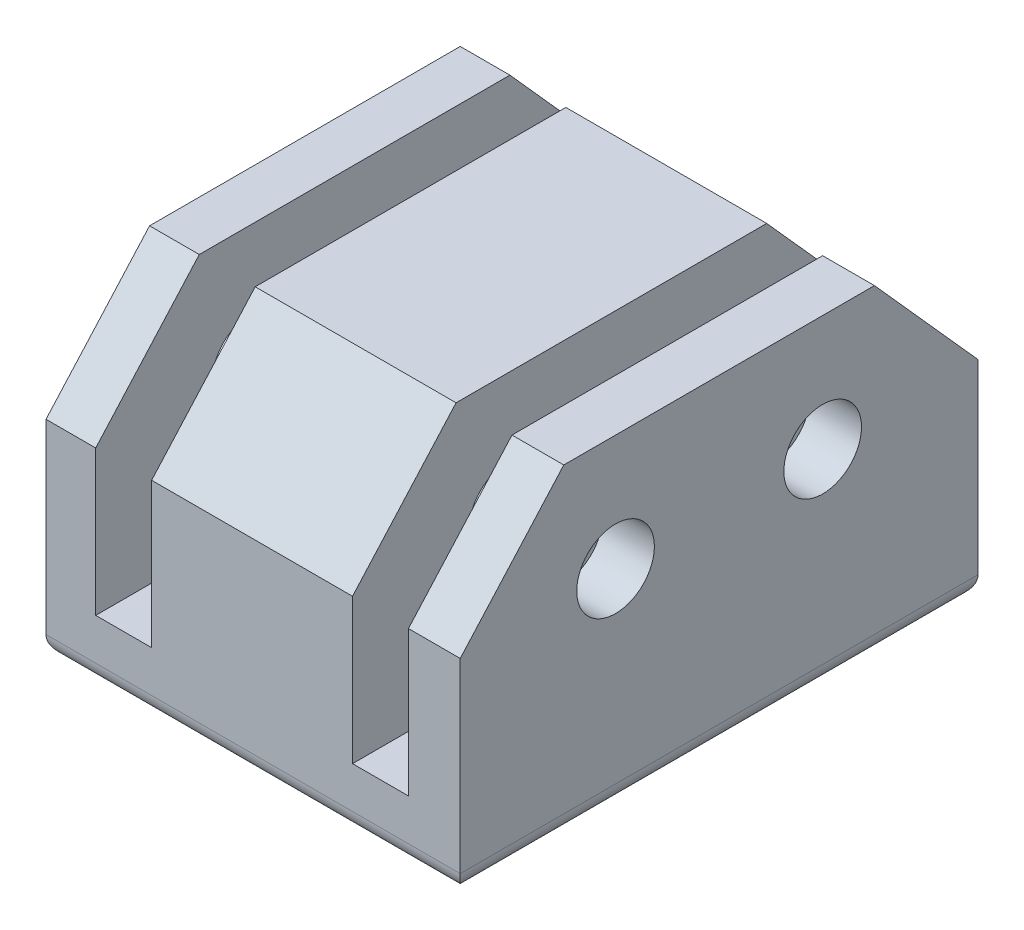
SolidWorks part; units mm, degrees
ref_plane "Front Plane" through (0, 0, 0) normal (0, 0, 1) x (1, 0, 0)
ref_plane "Top Plane" through (0, 0, 0) normal (0, 1, 0) x (1, 0, 0)
ref_plane "Right Plane" through (0, 0, 0) normal (1, 0, 0) x (0, 0, -1)
sketch "Sketch1" plane through (0, 0, 0) normal (1, 0, 0) x (0, 0, -1)
  line L1 (0, 0) -> (63.5, 0)
  line L2 (0, 0) -> (0, 6.35)
  line L3 (0, 6.35) -> (63.5, 6.35)
  line L4 (63.5, 0) -> (63.5, 6.35)
  dimension "D1" = 6.35
  dimension "D2" = 63.5
extrude "Boss-Extrude1" add sketch "Sketch1" against normal blind 50.8
sketch "Sketch2" plane through (0, 0, 0) normal (1, 0, 0) x (0, 0, -1)
  line L0 (0, 6.35) -> (0, 25.4)
  line L1 (0, 25.4) -> (12.7, 39.599)
  line L2 (12.7, 39.599) -> (50.8, 39.599)
  line L3 (50.8, 39.599) -> (63.5, 25.4)
  line L4 (63.5, 25.4) -> (63.5, 6.35)
  line L5 (63.5, 6.35) -> (0, 6.35)
  point P7 (31.75, 39.599)
  point P10 (31.75, 6.35)
  dimension "D1" = 38.1
  dimension "D2" = 19.05
  dimension "D4" = 19.05
  dimension "D5" = 19.05
extrude "Boss-Extrude2" add sketch "Sketch2" against normal blind 50.8
sketch "Sketch10" plane through (0, 0, -63.5) normal (0, 0, -1) x (-1, 0, 0)
  line L1 (50.8, 39.599) -> (0, 39.599) construction
  line L3 (6.35, 7.62) -> (6.35, 39.599)
  line L4 (6.35, 39.599) -> (13.208, 39.599)
  line L5 (13.208, 7.62) -> (13.208, 39.599)
  line L6 (6.35, 7.62) -> (13.208, 7.62)
  line L8 (50.8, 0) -> (0, 0) construction
  point P11 (13.208, 7.62)
  dimension "D1" = 7.62
  dimension "D2" = 6.858
  dimension "D3" = 6.35
extrude "Cut-Extrude1" cut sketch "Sketch10" against normal through all
pattern_linear "LPattern3" count 2 spacing 31.496 along (-1, 0, 0) of "Cut-Extrude1"
sketch "Sketch11" plane through (0, 0, 0) normal (1, 0, 0) x (0, 0, -1)
  circle A0 centre (19.05, 25.4) radius 4.7625
  circle A1 centre (19.05, 25.4) radius 7.9375 construction
  circle A2 centre (44.45, 25.4) radius 4.7625
  circle A3 centre (44.45, 25.4) radius 7.9375 construction
  dimension "D1" = 9.525
  dimension "D3" = 15.875
  dimension "D4" = 9.525
  dimension "D6" = 15.875
  dimension "D2" = 6.35
  dimension "D5" = 6.35
extrude "Cut-Extrude2" cut sketch "Sketch11" against normal through all
sketch "Sketch14" plane through (0, 39.599, 0) normal (0, 1, 0) x (1, 0, 0)
  line L3 (-37.846, 12.7) -> (-37.846, 50.8) construction
  point P0 (-25.4, 31.75)
  point P4 (-37.846, 31.75)
  dimension "D1" = 12.446
sketch "Sketch17" plane through (0, 42.8423, -47.8991) normal (0, 0.6667, -0.7454) x (-1, 0, 0)
  line L0 (13.208, -23.4013) -> (13.208, -4.3513) construction
  line L1 (37.846, -4.3513) -> (13.208, -4.3513) construction
  point P0 (25.527, -13.8763)
  point P4 (13.208, -13.8763)
  point P7 (25.527, -4.3513)
sketch "Sketch18" plane through (0, 11.2889, 12.6214) normal (0, 0.6667, 0.7454) x (1, 0, 0)
  line L0 (-13.208, 37.982) -> (-13.208, 18.932) construction
  line L1 (-37.846, 37.982) -> (-13.208, 37.982) construction
  point P0 (-25.527, 28.457)
  point P1 (-25.527, 28.457)
  point P4 (-13.208, 28.457)
  point P7 (-25.527, 37.982)
ref_plane "Plane2" through (0, 33.02, 0) normal (0, -1, 0) x (-1, 0, 0)
ref_plane "midplane" through (0, 0, -31.75) normal (0, 0, -1) x (-1, 0, 0)
fillet "Fillet1" radius 2.54 4 edges at (0, 0, -31.75) (-25.4, 0, -63.5) (-50.8, 0, -31.75) (-25.4, 0, 0)
sketch "Sketch19" plane through (0, 0, 0) normal (0, -1, 0) x (1, 0, 0)
  line L0 (-25.4, -63.5) -> (-25.4, 0) construction
  line L1 (0, -63.5) -> (-50.8, -63.5) construction
  line L2 (-50.8, 0) -> (0, 0) construction
  line L3 (0, -31.75) -> (-50.8, -31.75) construction
  line L4 (0, 0) -> (0, -63.5) construction
  line L5 (-50.8, -63.5) -> (-50.8, 0) construction
  line L7 (-9.525, -50.8) -> (-41.275, -50.8) construction
  line L8 (-9.525, -50.8) -> (-9.525, -12.7) construction
  line L9 (-9.525, -12.7) -> (-41.275, -12.7) construction
  line L10 (-41.275, -50.8) -> (-41.275, -12.7) construction
  line L11 (-9.525, -50.8) -> (-41.275, -12.7) construction
  line L12 (-9.525, -12.7) -> (-41.275, -50.8) construction
  circle A0 centre (-9.525, -50.8) radius 1.778
  circle A1 centre (-41.275, -50.8) radius 1.778
  circle A2 centre (-41.275, -12.7) radius 1.778
  circle A3 centre (-9.525, -12.7) radius 1.778
  point P12 (-25.4, -31.75)
  dimension "D3" = 3.556
  dimension "D1" = 31.75
  dimension "D2" = 38.1
extrude "Cut-Extrude3" cut sketch "Sketch19" against normal up to surface (7.62 mm away) up to face at (-9.779, 7.62, -31.75)
